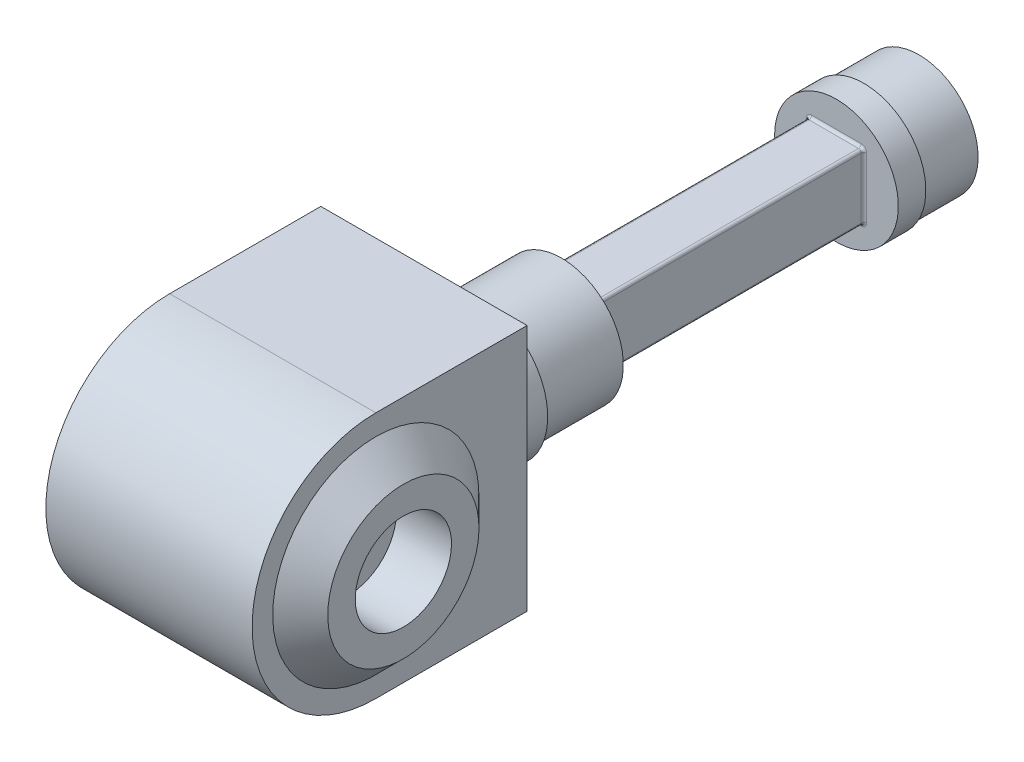
SolidWorks part; units mm, degrees
ref_plane "Front Plane" through (0, 0, 0) normal (0, 0, 1) x (1, 0, 0)
ref_plane "Top Plane" through (0, 0, 0) normal (0, 1, 0) x (1, 0, 0)
ref_plane "Right Plane" through (0, 0, 0) normal (1, 0, 0) x (0, 0, -1)
sketch "Sketch1" plane through (0, 0, 0) normal (0, 0, 1) x (1, 0, 0)
  line L1 (-37.5, 45) -> (37.5, 45)
  line L2 (-37.5, 45) -> (-37.5, -45)
  line L3 (-37.5, -45) -> (37.5, -45)
  line L4 (37.5, 45) -> (37.5, -45)
  line L5 (-37.5, 45) -> (37.5, -45) construction
  line L6 (-37.5, -45) -> (37.5, 45) construction
  point P0 (0, 0)
  dimension "D1" = 90
  dimension "D2" = 75
extrude "Boss-Extrude1" add sketch "Sketch1" along normal mid plane 100
sketch "Sketch2" plane through (0, 0, -50) normal (0, 0, -1) x (-1, 0, 0)
  line L4 (-37.5, 45) -> (-37.5, -45)
  line L5 (-37.5, -45) -> (37.5, -45)
  line L6 (37.5, -45) -> (37.5, 45)
  line L7 (37.5, 45) -> (-37.5, 45)
  line L8 (-37.5, 45) -> (-37.5, -45)
  line L9 (-37.5, -45) -> (37.5, -45)
  line L10 (37.5, -45) -> (37.5, 45)
  line L11 (37.5, 45) -> (-37.5, 45)
  dimension "D1" = 0
extrude "Boss-Extrude2" add sketch "Sketch2" along normal blind 10 draft 45
sketch "Sketch3" plane through (0, 0, -60) normal (0, 0, -1) x (-1, 0, 0)
  circle A0 centre (0, 0) radius 25
  dimension "D1" = 50
extrude "Boss-Extrude3" add sketch "Sketch3" along normal blind 10
sketch "Sketch4" plane through (0, 0, -70) normal (0, 0, -1) x (-1, 0, 0)
  circle A0 centre (0, 0) radius 22.5
  dimension "D1" = 45
extrude "Boss-Extrude4" add sketch "Sketch4" along normal blind 30
sketch "Sketch5" plane through (0, 0, -100) normal (0, 0, -1) x (-1, 0, 0)
  line L0 (0, 0) -> (22.5, 0) construction
  circle A0 centre (0, 0) radius 22.5 construction
  circle A1 centre (18, 0) radius 2.5
  dimension "D2" = 5
  dimension "D1" = 18
extrude "Cut-Extrude1" cut sketch "Sketch5" against normal blind 5
pattern_circular "CirPattern1" count 10 over 360 about axis through (0, 0, -100) along (0, 0, -1) of "Cut-Extrude1"
sketch "Sketch6" plane through (0, 0, -100) normal (0, 0, -1) x (-1, 0, 0)
  line L1 (-10, 12) -> (10, 12)
  line L2 (-10, 12) -> (-10, -12)
  line L3 (-10, -12) -> (10, -12)
  line L4 (10, 12) -> (10, -12)
  line L5 (-10, 12) -> (10, -12) construction
  line L6 (-10, -12) -> (10, 12) construction
  point P0 (0, 0)
  dimension "D1" = 24
  dimension "D2" = 20
extrude "Boss-Extrude5" add sketch "Sketch6" along normal blind 100
sketch "Sketch7" plane through (0, 0, -200) normal (0, 0, -1) x (-1, 0, 0)
  circle A1 centre (0, 0) radius 22.5
extrude "Boss-Extrude6" add sketch "Sketch7" along normal blind 10
sketch "Sketch8" plane through (0, 0, -210) normal (0, 0, -1) x (-1, 0, 0)
  circle A0 centre (0, 0) radius 21.5
  circle A1 centre (0, 0) radius 22.5 construction
  dimension "D1" = 1
extrude "Boss-Extrude7" add sketch "Sketch8" along normal blind 20
sketch "Sketch9" plane through (0, 0, -230) normal (0, 0, -1) x (-1, 0, 0)
  circle A0 centre (0, 0) radius 10
  dimension "D1" = 20
extrude "Cut-Extrude2" cut sketch "Sketch9" against normal blind 10
fillet "Fillet1" 2 edges at (0, 45, 50) (0, -45, 50) type full round first side face at (0, 45, 0) second side face at (0, -45, 0) middle face at (0, 0, 50)
sketch "Sketch10" plane through (37.5, 0, 0) normal (1, 0, 0) x (0, 0, -1)
  circle A0 centre (-5, 0) radius 37.5
  dimension "D1" = 75
extrude "Boss-Extrude8" add sketch "Sketch10" along normal blind 10 draft 45
sketch "Sketch11" plane through (47.5, 0, 0) normal (1, 0, 0) x (0, 0, -1)
  circle A0 centre (-5, 0) radius 17.5
  dimension "D1" = 35
extrude "Cut-Extrude3" cut sketch "Sketch11" against normal blind 20
fillet "Fillet4" radius 1 1 edges at (-25, 0, -60)
fillet "Fillet5" radius 1 12 edges at (0, 12, -200) (0, 12, -100) (0, -12, -200) (0, -12, -100) (-10, -12, -150) (-10, 0, -200) (-10, 12, -150) (-10, 0, -100) (10, 12, -150) (10, 0, -200) (10, -12, -150) (10, 0, -100)
